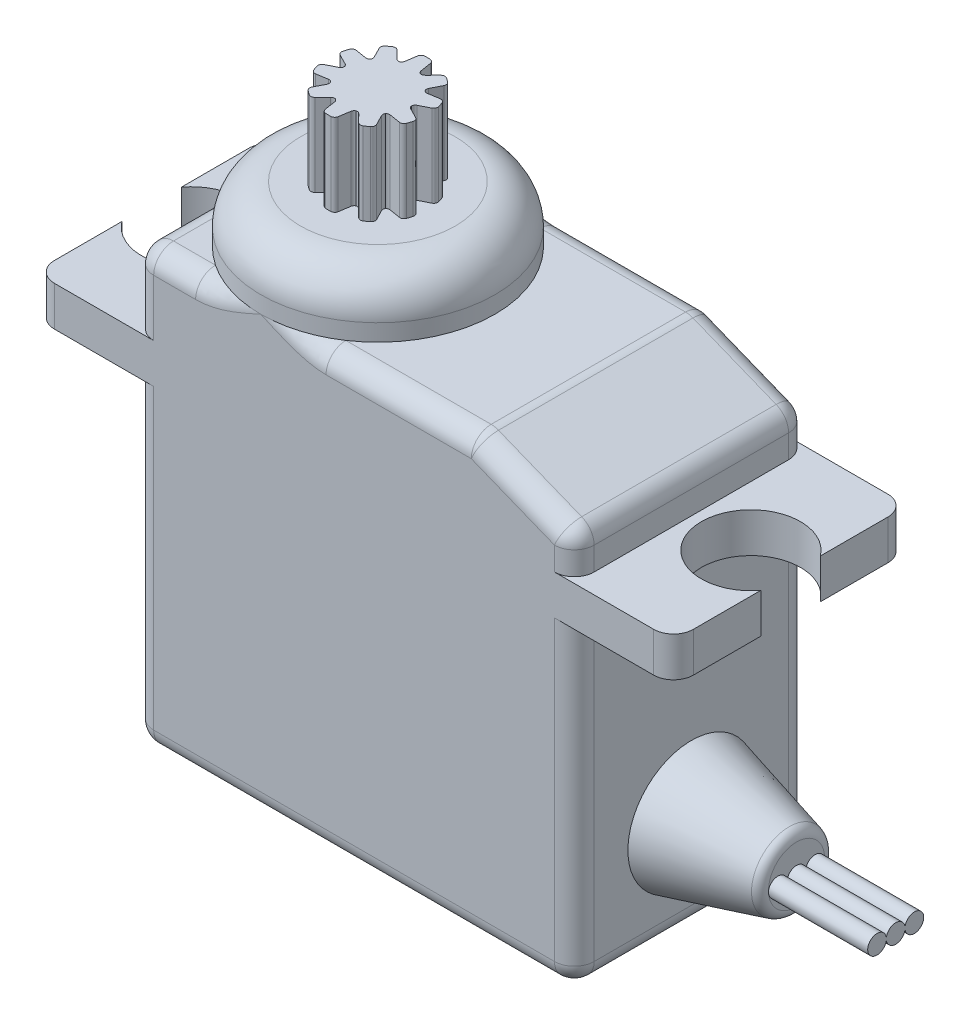
SolidWorks part; units mm, degrees
ref_plane "Plan de face" through (0, 0, 0) normal (0, 0, 1) x (1, 0, 0)
ref_plane "Plan de dessus" through (0, 0, 0) normal (0, 1, 0) x (1, 0, 0)
ref_plane "Plan de droite" through (0, 0, 0) normal (1, 0, 0) x (0, 0, -1)
sketch "Esquisse1" plane through (0, 0, 0) normal (0, 0, 1) x (1, 0, 0)
  line L1 (11.1, -10.925) -> (-11.1, -10.925)
  line L2 (11.1, -10.925) -> (11.1, 5.075)
  line L4 (-11.1, -10.925) -> (-11.1, 5.075)
  line L5 (11.1, -10.925) -> (-11.1, 10.925) construction
  line L6 (9.6552, 9.5029) -> (-11.1, -10.925) construction
  line L7 (-11.1, 7.075) -> (-16.1, 7.075)
  line L8 (-11.1, 7.075) -> (-11.1, 5.075) construction
  line L9 (-11.1, 5.075) -> (-16.1, 5.075)
  line L10 (-16.1, 7.075) -> (-16.1, 5.075)
  line L11 (-11.1, 5.075) -> (11.1, 5.075) construction
  line L13 (11.1, 5.075) -> (16.1, 5.075)
  line L14 (11.1, 5.075) -> (11.1, 7.075) construction
  line L15 (11.1, 7.075) -> (16.1, 7.075)
  line L16 (16.1, 5.075) -> (16.1, 7.075)
  line L17 (11.1, 8.925) -> (6.1, 10.925)
  line L19 (-11.1, 10.925) -> (-2.0755, 10.925)
  line L20 (-2.0755, 10.925) -> (6.1, 10.925)
  line L21 (11.1, 10.925) -> (6.1, 10.925) construction
  line L22 (11.1, 10.925) -> (9.6552, 9.5029) construction
  line L23 (11.1, 8.925) -> (11.1, 10.925) construction
  line L24 (-11.1, 5.075) -> (-11.1, 7.075) construction
  line L25 (-11.1, 7.075) -> (-11.1, 10.925)
  line L26 (11.1, 5.075) -> (11.1, 7.075) construction
  line L27 (11.1, 7.075) -> (11.1, 8.925)
  point P0 (0, 0)
  point P10 (0, 0)
  point P17 (0, 0)
  point P20 (-11.1188, 10.9064)
  dimension "D1" = 22.2
  dimension "D2" = 21.85
  dimension "D3" = 16
  dimension "D4" = 32.2
  dimension "D5" = 2
  dimension "D6" = 2
  dimension "D9" = 2
  dimension "D10" = 5
extrude "Boss.-Extru.1" add sketch "Esquisse1" along normal blind 5.9 and the other way blind 5.9
sketch "Esquisse3" plane through (0, 0, 0) normal (0, 0, 1) x (1, 0, 0)
  line L0 (-4.7, 10.925) -> (-4.7, 17.925) construction
  line L2 (-4.7, 17.925) -> (-7.2, 17.925)
  line L3 (-7.2, 17.925) -> (-7.2, 13.775)
  line L4 (-7.2, 13.775) -> (-10.6, 13.775)
  line L5 (-10.6, 13.775) -> (-10.6, 10.925)
  line L6 (-10.6, 10.925) -> (-4.7, 10.925)
  line L7 (-4.7, 10.925) -> (-4.7, 17.925)
  line L8 (6.1, 10.925) -> (-11.1, 10.925) construction
  point P1 (-4.521, 10.925)
  point P6 (-21.0143, 36.8433)
  point P10 (-13.9506, 29.5)
  point P12 (0, 0)
  point P13 (0, 0)
  dimension "D1" = 7
  dimension "D2" = 4.7
  dimension "D3" = 2.5
  dimension "D4" = 3.4
  dimension "D5" = 2.85
revolve "Révolution1" add sketch "Esquisse3" angle 360 about L0
sketch "Esquisse4" plane through (0, 17.925, 0) normal (0, 1, 0) x (1, 0, 0)
  line L0 (-4.7, 0) -> (-4.7, 2.5) construction
  line L1 (-4.7, 0) -> (-5.4725, 2.3776) construction
  line L2 (-5.0235, 2.3272) -> (-5.11, 1.7696)
  line L3 (-5.8062, 2.0729) -> (-5.4084, 1.6726)
  line L4 (-4.3765, 2.3272) -> (-4.29, 1.7696)
  line L5 (-3.5938, 2.0729) -> (-3.9916, 1.6726)
  line L6 (-3.0704, 1.6926) -> (-3.3282, 1.1906)
  line L7 (-2.5866, 1.0268) -> (-3.1437, 0.9367)
  line L8 (-2.3867, 0.4115) -> (-2.8904, 0.1569)
  line L9 (-2.3867, -0.4115) -> (-2.8904, -0.1569)
  line L10 (-2.5866, -1.0268) -> (-3.1437, -0.9367)
  line L11 (-3.0704, -1.6926) -> (-3.3282, -1.1906)
  line L12 (-3.5938, -2.0729) -> (-3.9916, -1.6726)
  line L13 (-4.3765, -2.3272) -> (-4.29, -1.7696)
  line L14 (-5.0235, -2.3272) -> (-5.11, -1.7696)
  line L15 (-5.8062, -2.0729) -> (-5.4084, -1.6726)
  line L16 (-6.3296, -1.6926) -> (-6.0718, -1.1906)
  line L17 (-6.8134, -1.0268) -> (-6.2563, -0.9367)
  line L18 (-7.0133, -0.4115) -> (-6.5096, -0.1569)
  line L19 (-7.0133, 0.4115) -> (-6.5096, 0.1569)
  line L20 (-6.8134, 1.0268) -> (-6.2563, 0.9367)
  line L21 (-6.3296, 1.6926) -> (-6.0718, 1.1906)
  circle A0 centre (-4.7, 0) radius 2.5 construction
  arc A1 (-5.2437, 1.6107) -> (-5.2069, 1.6227) centre (-4.7, 0) ccw
  arc A2 (-4.7, 2.5) -> (-4.8368, 2.4963) centre (-4.7, 0) ccw
  arc A3 (-5.11, 1.7696) -> (-5.2437, 1.6107) centre (-5.3076, 1.8002) cw
  arc A4 (-5.0235, 2.3272) -> (-4.8368, 2.4963) centre (-4.8258, 2.2966) cw
  arc A5 (-5.4084, 1.6726) -> (-5.2069, 1.6227) centre (-5.2666, 1.8136) ccw
  arc A6 (-6.1695, 2.0225) -> (-6.0566, 2.0999) centre (-4.7, 0) cw
  arc A7 (-5.8062, 2.0729) -> (-6.0566, 2.0999) centre (-5.9481, 1.9319) ccw
  arc A8 (-4.7, 2.5) -> (-4.5632, 2.4963) centre (-4.7, 0) cw
  arc A9 (-4.3765, 2.3272) -> (-4.5632, 2.4963) centre (-4.5742, 2.2966) ccw
  arc A10 (-4.29, 1.7696) -> (-4.1563, 1.6107) centre (-4.0924, 1.8002) ccw
  arc A11 (-4.1931, 1.6227) -> (-4.1563, 1.6107) centre (-4.7, 0) ccw
  arc A12 (-3.9916, 1.6726) -> (-4.1931, 1.6227) centre (-4.1334, 1.8136) cw
  arc A13 (-3.5938, 2.0729) -> (-3.3434, 2.0999) centre (-3.4519, 1.9319) cw
  arc A14 (-3.2305, 2.0225) -> (-3.3434, 2.0999) centre (-4.7, 0) ccw
  arc A15 (-3.2305, 2.0225) -> (-3.1221, 1.9391) centre (-4.7, 0) cw
  arc A16 (-3.0704, 1.6926) -> (-3.1221, 1.9391) centre (-3.2483, 1.784) ccw
  arc A17 (-3.3282, 1.1906) -> (-3.3134, 0.9836) centre (-3.1503, 1.0993) ccw
  arc A18 (-3.3361, 1.0148) -> (-3.3134, 0.9836) centre (-4.7, 0) ccw
  arc A19 (-3.1437, 0.9367) -> (-3.3361, 1.0148) centre (-3.1756, 1.1342) cw
  arc A20 (-2.5866, 1.0268) -> (-2.3682, 0.9015) centre (-2.5547, 0.8294) cw
  arc A21 (-2.3224, 0.7725) -> (-2.3682, 0.9015) centre (-4.7, 0) ccw
  arc A22 (-2.3224, 0.7725) -> (-2.2837, 0.6413) centre (-4.7, 0) cw
  arc A23 (-2.3867, 0.4115) -> (-2.2837, 0.6413) centre (-2.477, 0.59) ccw
  arc A24 (-2.8904, 0.1569) -> (-3.0001, -0.0193) centre (-2.8001, -0.0216) ccw
  arc A25 (-3.0001, 0.0193) -> (-3.0001, -0.0193) centre (-4.7, 0) ccw
  arc A26 (-2.8904, -0.1569) -> (-3.0001, 0.0193) centre (-2.8001, 0.0216) cw
  arc A27 (-2.3867, -0.4115) -> (-2.2837, -0.6413) centre (-2.477, -0.59) cw
  arc A28 (-2.3224, -0.7725) -> (-2.2837, -0.6413) centre (-4.7, 0) ccw
  arc A29 (-2.3224, -0.7725) -> (-2.3682, -0.9015) centre (-4.7, 0) cw
  arc A30 (-2.5866, -1.0268) -> (-2.3682, -0.9015) centre (-2.5547, -0.8294) ccw
  arc A31 (-3.1437, -0.9367) -> (-3.3361, -1.0148) centre (-3.1756, -1.1342) ccw
  arc A32 (-3.3134, -0.9836) -> (-3.3361, -1.0148) centre (-4.7, 0) ccw
  arc A33 (-3.3282, -1.1906) -> (-3.3134, -0.9836) centre (-3.1503, -1.0993) cw
  arc A34 (-3.0704, -1.6926) -> (-3.1221, -1.9391) centre (-3.2483, -1.784) cw
  arc A35 (-3.2305, -2.0225) -> (-3.1221, -1.9391) centre (-4.7, 0) ccw
  arc A36 (-3.2305, -2.0225) -> (-3.3434, -2.0999) centre (-4.7, 0) cw
  arc A37 (-3.5938, -2.0729) -> (-3.3434, -2.0999) centre (-3.4519, -1.9319) ccw
  arc A38 (-3.9916, -1.6726) -> (-4.1931, -1.6227) centre (-4.1334, -1.8136) ccw
  arc A39 (-4.1563, -1.6107) -> (-4.1931, -1.6227) centre (-4.7, 0) ccw
  arc A40 (-4.29, -1.7696) -> (-4.1563, -1.6107) centre (-4.0924, -1.8002) cw
  arc A41 (-4.3765, -2.3272) -> (-4.5632, -2.4963) centre (-4.5742, -2.2966) cw
  arc A42 (-4.7, -2.5) -> (-4.5632, -2.4963) centre (-4.7, 0) ccw
  arc A43 (-4.7, -2.5) -> (-4.8368, -2.4963) centre (-4.7, 0) cw
  arc A44 (-5.0235, -2.3272) -> (-4.8368, -2.4963) centre (-4.8258, -2.2966) ccw
  arc A45 (-5.11, -1.7696) -> (-5.2437, -1.6107) centre (-5.3076, -1.8002) ccw
  arc A46 (-5.2069, -1.6227) -> (-5.2437, -1.6107) centre (-4.7, 0) ccw
  arc A47 (-5.4084, -1.6726) -> (-5.2069, -1.6227) centre (-5.2666, -1.8136) cw
  arc A48 (-5.8062, -2.0729) -> (-6.0566, -2.0999) centre (-5.9481, -1.9319) cw
  arc A49 (-6.1695, -2.0225) -> (-6.0566, -2.0999) centre (-4.7, 0) ccw
  arc A50 (-6.1695, -2.0225) -> (-6.2779, -1.9391) centre (-4.7, 0) cw
  arc A51 (-6.3296, -1.6926) -> (-6.2779, -1.9391) centre (-6.1517, -1.784) ccw
  arc A52 (-6.0718, -1.1906) -> (-6.0866, -0.9836) centre (-6.2497, -1.0993) ccw
  arc A53 (-6.0639, -1.0148) -> (-6.0866, -0.9836) centre (-4.7, 0) ccw
  arc A54 (-6.2563, -0.9367) -> (-6.0639, -1.0148) centre (-6.2244, -1.1342) cw
  arc A55 (-6.8134, -1.0268) -> (-7.0318, -0.9015) centre (-6.8453, -0.8294) cw
  arc A56 (-7.0776, -0.7725) -> (-7.0318, -0.9015) centre (-4.7, 0) ccw
  arc A57 (-7.0776, -0.7725) -> (-7.1163, -0.6413) centre (-4.7, 0) cw
  arc A58 (-7.0133, -0.4115) -> (-7.1163, -0.6413) centre (-6.923, -0.59) ccw
  arc A59 (-6.5096, -0.1569) -> (-6.3999, 0.0193) centre (-6.5999, 0.0216) ccw
  arc A60 (-6.3999, -0.0193) -> (-6.3999, 0.0193) centre (-4.7, 0) ccw
  arc A61 (-6.5096, 0.1569) -> (-6.3999, -0.0193) centre (-6.5999, -0.0216) cw
  arc A62 (-7.0133, 0.4115) -> (-7.1163, 0.6413) centre (-6.923, 0.59) cw
  arc A63 (-7.0776, 0.7725) -> (-7.1163, 0.6413) centre (-4.7, 0) ccw
  arc A64 (-7.0776, 0.7725) -> (-7.0318, 0.9015) centre (-4.7, 0) cw
  arc A65 (-6.8134, 1.0268) -> (-7.0318, 0.9015) centre (-6.8453, 0.8294) ccw
  arc A66 (-6.2563, 0.9367) -> (-6.0639, 1.0148) centre (-6.2244, 1.1342) ccw
  arc A67 (-6.0866, 0.9836) -> (-6.0639, 1.0148) centre (-4.7, 0) ccw
  arc A68 (-6.0718, 1.1906) -> (-6.0866, 0.9836) centre (-6.2497, 1.0993) cw
  arc A69 (-6.3296, 1.6926) -> (-6.2779, 1.9391) centre (-6.1517, 1.784) cw
  arc A70 (-6.1695, 2.0225) -> (-6.2779, 1.9391) centre (-4.7, 0) ccw
  circle A71 centre (-4.7, 0) radius 5
  point P12 (-5.1293, 1.6449)
  point P15 (-4.9995, 2.482)
  point P150 (-4.7, 0)
  circle M93 centre (-4.7, 0) radius 2.5
  dimension "D1" = 0.8
  dimension "D5" = 0.2
  dimension "D7" = 10
  dimension "D2" = 18
  dimension "D3" = 0.3
  dimension "D4" = 0.1
  dimension "D6" = 10
extrude "Enlèv. mat.-Extru.1" cut sketch "Esquisse4" against normal up to surface (4.15 mm away) contours A71 M93 | L17 A55 A51 L16 A52 A53 A54 M93 | L19 A62 A58 L18 A59 A60 A61 M93 | L21 A69 A65 L20 A66 A67 A68 M93 | A7 L3 A5 A1 A3 L2 A4 M93 | L5 A13 A9 L4 A10 A11 A12 M93 | L7 A20 A16 L6 A17 A18 A19 M93 | L9 A27 A23 L8 A24 A25 A26 M93 | L11 A34 A30 L10 A31 A32 A33 M93 | L13 A41 A37 L12 A38 A39 A40 M93 | L15 A48 A44 L14 A45 A46 A47 M93 region at (-5.3762, 17.925, -2.0812) region at (-4.0238, 17.925, -2.0812) region at (-6.4704, 17.925, -1.2862) region at (-2.9296, 17.925, -1.2862) region at (-6.8883, 17.925, 0) region at (-6.4704, 17.925, 1.2862) region at (-2.5117, 17.925, 0) region at (-5.3762, 17.925, 2.0812) region at (-2.9296, 17.925, 1.2862) region at (-4.0238, 17.925, 2.0812) region at (-9.5586, 17.925, 0) up to face at (1.2, 13.775, 0)
fillet "Congé2" radius 1 23 edges at (16.1, 6.075, -5.9) (11.1, 8, -5.9) (-11.1, 9, -5.9) (-16.1, 6.075, -5.9) (-11.1, -2.925, -5.9) (0, -10.925, -5.9) (11.1, -2.925, -5.9) (0, -10.925, 5.9) (-11.1, -2.925, 5.9) (-16.1, 6.075, 5.9) (-11.1, 9, 5.9) (11.1, 8, 5.9) (16.1, 6.075, 5.9) (11.1, -2.925, 5.9) (8.6, 9.925, -5.9) (11.1, 8.925, 0) (8.6, 9.925, 5.9) (11.1, -10.925, 0) (-11.1, -10.925, 0) (-7.9, 10.925, -5.9) (-7.9, 10.925, 5.9) (6.1, 10.925, 0) (-11.1, 10.925, 0)
fillet "Congé3" radius 2 1 edges at (1.2, 13.775, 0)
sketch "Esquisse5" plane through (0, 0, 0) normal (0, 0, 1) x (1, 0, 0)
  line L0 (10.1, -9.925) -> (10.1, -5.925) construction
  line L1 (10.1, -9.925) -> (10.1, 5.075) construction
  line L2 (10.1, -5.925) -> (11.1, -5.925) construction
  line L3 (16.4, -5.925) -> (16.4, -7.725)
  line L4 (16.4, -7.725) -> (11.1, -9.125)
  line L5 (11.1, 5.075) -> (11.1, -9.925) construction
  line L6 (11.1, -9.125) -> (11.1, -5.925)
  line L7 (11.1, -5.925) -> (16.4, -5.925)
  point P11 (31.9, -22.9994)
  dimension "D1" = 5.3
  dimension "D2" = 1.8
  dimension "D3" = 3.2
  dimension "D4" = 4
revolve "Révolution2" add sketch "Esquisse5" angle 360 about L7
fillet "Congé4" radius 0.5 1 edges at (16.4, -7.725, 0)
ref_plane "Plan1" through (0, -6, 0) normal (0, 1, 0) x (1, 0, 0)
sketch "Esquisse6" plane through (0, -6, 0) normal (0, 1, 0) x (1, 0, 0)
  line L0 (31.4781, -2.1829) -> (31.4781, 2.1829) construction
  line L1 (16.0277, 1.8983) -> (11.1, 3.2) construction
  line L2 (11.1, -3.2) -> (16.0277, -1.8983) construction
  line L3 (31.4781, 0) -> (13.9, 0) construction
  line L4 (16.4, -1.4149) -> (16.4, 1.4149) construction
  line L5 (16.4, 0.4716) -> (16.4, 0) construction
  line L6 (16.4, -1.4149) -> (13.9, -1.4149) construction
  line L7 (13.9, -1.4149) -> (13.9, -0.4716) construction
  line L8 (13.9, 0) -> (13.9, 0.4716) construction
  line L9 (16.4, 0) -> (21.4, 0) construction
  line L10 (13.9, 0.9433) -> (13.9, 1.4149) construction
  line L11 (13.9, 1.4149) -> (16.4, 1.4149) construction
  line L12 (21.4, 0) -> (21.4, -0.4716) construction
  line L13 (21.4, -0.4716) -> (16.4, -0.4716) construction
  line L14 (13.9, 0) -> (13.9, -0.4716) construction
  line L15 (13.9, -1.4149) -> (21.4, -1.4149)
  line L16 (21.4, -1.4149) -> (21.4, -0.9433)
  line L17 (21.4, -0.9433) -> (13.9, -0.9433)
  line L18 (13.9, -0.9433) -> (13.9, -1.4149)
  line L19 (13.9, 0.9433) -> (16.4, 0.9433) construction
  line L20 (21.4, 0.9433) -> (21.4, 0.4716) construction
  line L21 (21.4, 0.4716) -> (16.4, 0.4716) construction
  line L22 (13.9, 0.4716) -> (13.9, 0.9433) construction
  line L23 (13.9, 0.4716) -> (13.9, 0.9433) construction
  line L24 (16.4, 0.4716) -> (13.9, 0.4716) construction
  line L25 (13.9, 0) -> (16.4, 0) construction
  line L26 (13.9, 0) -> (16.4, 0) construction
  line L27 (13.9, -0.4716) -> (13.9, 0) construction
  line L28 (16.4, -0.4716) -> (13.9, -0.4716) construction
  line L29 (16.4, 0) -> (16.4, -0.4716) construction
  line L30 (16.4, -0.4716) -> (16.4, -1.4149) construction
  line L31 (16.4, 0.9433) -> (21.4, 0.9433) construction
  line L32 (16.4, 1.4149) -> (16.4, 0.9433) construction
  line L33 (16.4, 0.9433) -> (16.4, 0.4716) construction
  arc A0 (16.4, 1.4149) -> (16.0277, 1.8983) centre (15.9, 1.4149) ccw construction
  arc A1 (16.0277, -1.8983) -> (16.4, -1.4149) centre (15.9, -1.4149) ccw construction
  dimension "D1" = 2.5
  dimension "D2" = 0.9433
  dimension "D3" = 0.9433
  dimension "D4" = 5
revolve "Révolution3" add sketch "Esquisse6" angle 360 about L17
pattern_linear "Répétition linéaire1" count 3 spacing 0.94 along (0, 0, -1) of "Révolution3"
sketch "Esquisse9" plane through (0, 0, 0) normal (0, 1, 0) x (1, 0, 0)
  line L0 (-16.1, 0) -> (-14.1, 0) construction
  line L1 (-16.1, 4.9) -> (-16.1, -4.9) construction
  line L2 (0, 0) -> (0, 5.9) construction
  line L3 (-1.4137, 5.9) -> (5.9074, 5.9) construction
  circle A0 centre (-14.1, 0) radius 2.5
  circle A1 centre (14.1, 0) radius 2.5
  dimension "D1" = 5
  dimension "D2" = 2
extrude "Enlèv. mat.-Extru.2" cut sketch "Esquisse9" along normal through all
